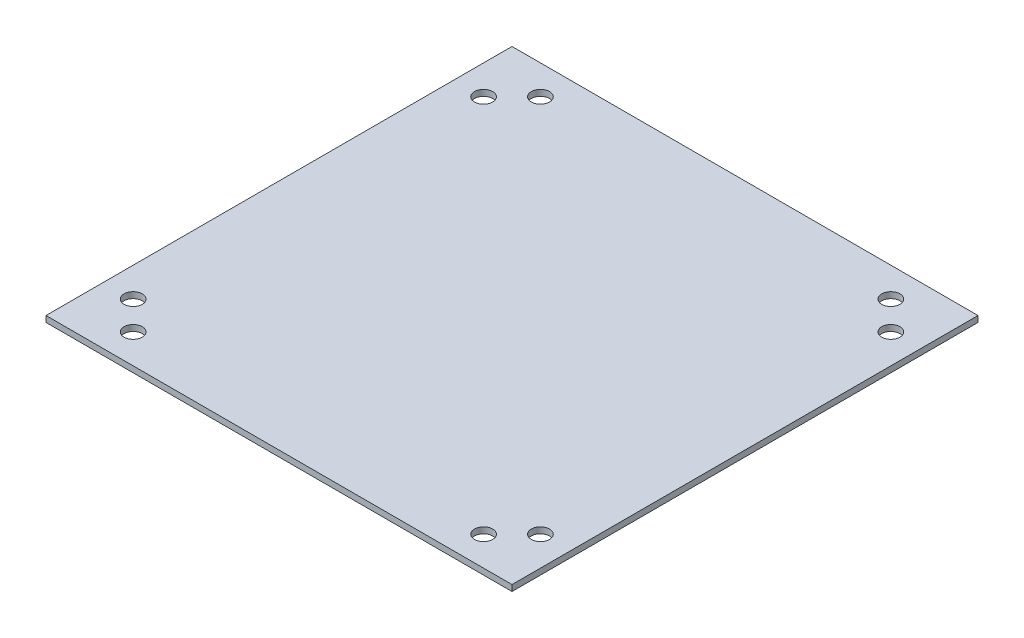
SolidWorks part; units mm, degrees
ref_plane "Front Plane" through (0, 0, 0) normal (0, 0, 1) x (1, 0, 0)
ref_plane "Top Plane" through (0, 0, 0) normal (0, 1, 0) x (1, 0, 0)
ref_plane "Right Plane" through (0, 0, 0) normal (1, 0, 0) x (0, 0, -1)
sketch "Sketch1" plane through (0, 0, 0) normal (0, 1, 0) x (1, 0, 0)
  line L1 (0, 0) -> (97.4, 0)
  line L2 (0, 0) -> (0, 97.4)
  line L3 (0, 97.4) -> (97.4, 97.4)
  line L4 (97.4, 0) -> (97.4, 97.4)
  line L5 (0, 0) -> (7.2, 0)
  line L6 (0, 0) -> (0, 7.2)
  line L7 (0, 7.2) -> (7.2, 7.2)
  line L8 (7.2, 0) -> (7.2, 7.2)
  line L9 (0, 97.4) -> (7.2, 97.4)
  line L10 (0, 97.4) -> (0, 90.2)
  line L11 (0, 90.2) -> (7.2, 90.2)
  line L12 (7.2, 97.4) -> (7.2, 90.2)
  line L13 (97.4, 97.4) -> (90.2, 97.4)
  line L14 (97.4, 97.4) -> (97.4, 90.2)
  line L15 (97.4, 90.2) -> (90.2, 90.2)
  line L16 (90.2, 97.4) -> (90.2, 90.2)
  line L17 (97.4, 0) -> (90.2, 0)
  line L18 (97.4, 0) -> (97.4, 7.2)
  line L19 (97.4, 7.2) -> (90.2, 7.2)
  line L20 (90.2, 0) -> (90.2, 7.2)
  dimension "D1" = 7.2
  dimension "D2" = 7.2
  dimension "D3" = 7.2
  dimension "D4" = 7.2
  dimension "D5" = 97.4
  dimension "D6" = 7.2
  dimension "D7" = 7.2
  dimension "D8" = 97.4
  dimension "D9" = 7.2
  dimension "D10" = 7.2
extrude "Boss-Extrude1" add sketch "Sketch1" along normal blind 1.3 contours L1 L20 L19 L4 L15 L16 L3 L12 L11 L2 L7 L8 region at (48.7, 0, -48.7)
sketch "Sketch3" plane through (0, 1.3, 0) normal (0, 1, 0) x (1, 0, 0)
  line L0 (0, 90.2) -> (0, 7.2)
  line L1 (0, 7.2) -> (7.2, 7.2)
  line L2 (7.2, 7.2) -> (7.2, 0)
  line L3 (7.2, 0) -> (7.2, 7.2) construction
  line L4 (7.2, 0) -> (90.2, 0)
  line L5 (90.2, 0) -> (90.2, 7.2)
  line L6 (90.2, 7.2) -> (97.4, 7.2)
  line L7 (97.4, 7.2) -> (97.4, 90.2)
  line L8 (97.4, 90.2) -> (90.2, 90.2)
  line L9 (90.2, 90.2) -> (90.2, 97.4)
  line L10 (90.2, 97.4) -> (7.2, 97.4)
  line L11 (7.2, 97.4) -> (7.2, 90.2)
  line L12 (0, 7.2) -> (0, 90.2) construction
  line L13 (-1.3, 98.7) -> (98.7, 98.7)
  line L14 (-1.3, 98.7) -> (-1.3, -1.3)
  line L15 (-1.3, -1.3) -> (98.7, -1.3)
  line L16 (98.7, 98.7) -> (98.7, -1.3)
  line L17 (7.2, 97.4) -> (90.2, 97.4) construction
  line L18 (97.4, 7.2) -> (97.4, 90.2) construction
  line L19 (7.2, 0) -> (90.2, 0) construction
  line L20 (7.2, 90.2) -> (0, 90.2)
  dimension "D1" = 1.3
  dimension "D2" = 1.3
  dimension "D3" = 1.3
  dimension "D4" = 1.3
extrude "Boss-Extrude3" add sketch "Sketch3" against normal blind 1.3 contours L13 L16 L15 L14
sketch "Sketch2" plane through (0, 0, 0) normal (0, -1, 0) x (1, 0, 0)
  line L0 (7.2, 0) -> (90.2, 0) construction
  line L1 (97.4, -7.2) -> (97.4, -90.2) construction
  line L2 (0, -7.2) -> (0, -90.2) construction
  line L3 (0, -90.2) -> (7.2, -90.2) construction
  line L4 (7.2, -97.4) -> (90.2, -97.4) construction
  line L5 (7.2, -97.4) -> (7.2, -90.2) construction
  line L6 (0, -7.2) -> (7.2, -7.2) construction
  line L7 (90.2, -97.4) -> (90.2, -90.2) construction
  line L8 (97.4, -90.2) -> (90.2, -90.2) construction
  line L9 (7.2, 0) -> (7.2, -7.2) construction
  line L10 (90.2, 0) -> (90.2, -7.2) construction
  line L11 (97.4, -7.2) -> (90.2, -7.2) construction
  circle A0 centre (92.4, -86.3) radius 1.95
  circle A1 centre (86.3, -92.4) radius 1.95
  circle A2 centre (11.1, -92.4) radius 1.95
  circle A3 centre (5, -86.3) radius 1.95
  circle A4 centre (5, -11.1) radius 1.95
  circle A5 centre (11.1, -5) radius 1.95
  circle A6 centre (86.3, -5) radius 1.95
  circle A7 centre (92.4, -11.1) radius 1.95
  dimension "D1" = 3.9
  dimension "D2" = 3.9
  dimension "D3" = 3.9
  dimension "D4" = 3.9
  dimension "D5" = 3.9
  dimension "D6" = 3.9
  dimension "D7" = 3.9
  dimension "D8" = 3.9
  dimension "D9" = 3.9
  dimension "D10" = 3.9
  dimension "D11" = 3.9
  dimension "D12" = 3.9
  dimension "D13" = 5
  dimension "D14" = 5
  dimension "D15" = 5
  dimension "D16" = 5
  dimension "D17" = 5
  dimension "D18" = 5
  dimension "D19" = 3.9
  dimension "D20" = 3.9
  dimension "D21" = 3.9
  dimension "D22" = 5
  dimension "D23" = 5
  dimension "D24" = 3.9
extrude "Cut-Extrude1" cut sketch "Sketch2" against normal blind 1.3
